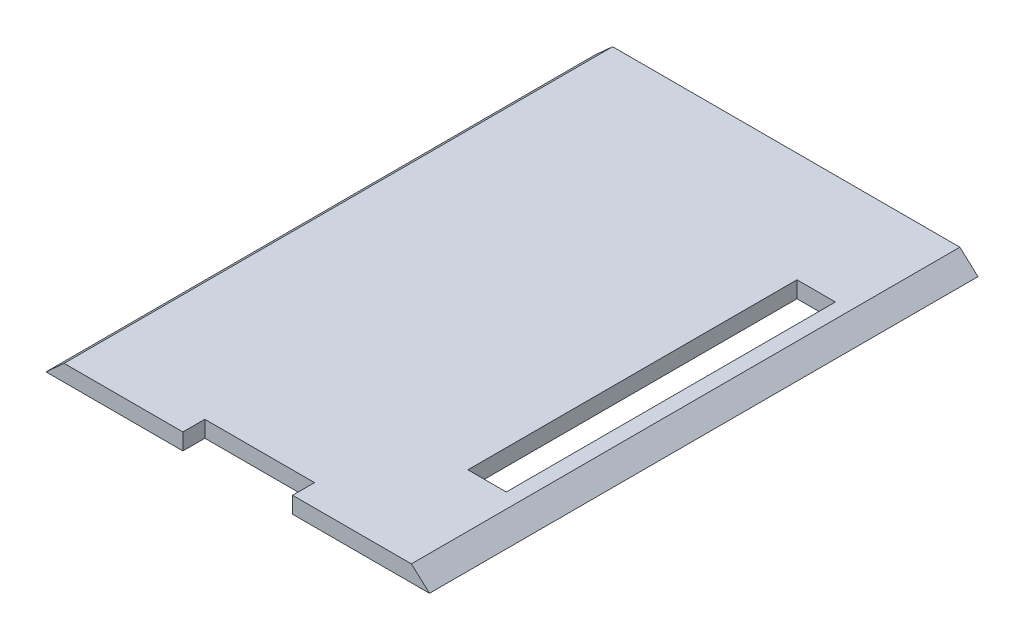
SolidWorks part; units mm, degrees
ref_plane "Front Plane" through (0, 0, 0) normal (0, 0, 1) x (1, 0, 0)
ref_plane "Top Plane" through (0, 0, 0) normal (0, 1, 0) x (1, 0, 0)
ref_plane "Right Plane" through (0, 0, 0) normal (1, 0, 0) x (0, 0, -1)
sketch "Sketch1" plane through (0, 0, 0) normal (0, 0, 1) x (1, 0, 0)
  line L0 (0, 0) -> (0, 44.45) construction
  line L1 (-40.2039, 5.9378) -> (40.2039, 5.9378)
  line L2 (-44.399, 2.1278) -> (44.399, 2.1278)
  line L3 (-40.2039, 5.9378) -> (-44.399, 2.1278)
  line L4 (40.2039, 5.9378) -> (44.399, 2.1278)
  arc A0 (44.399, 2.1278) -> (-44.399, 2.1278) centre (0, 0) ccw construction
  arc A1 (40.2039, 5.9378) -> (-40.2039, 5.9378) centre (0, 0) ccw construction
  dimension "D1" = 88.9
  dimension "D2" = 3.81
  dimension "D3" = 3.81
extrude "Boss-Extrude1" add sketch "Sketch1" along normal blind 127
sketch "Sketch3" plane through (0, 2.1278, 0) normal (0, -1, 0) x (1, 0, 0)
  line L0 (0, 127) -> (0, 0) construction
  line L1 (-44.399, 127) -> (44.399, 127) construction
  line L2 (-44.399, 0) -> (44.399, 0) construction
  line L3 (0, 63.5) -> (44.399, 63.5) construction
  line L4 (-12.7, 127) -> (12.7, 127)
  line L5 (-12.7, 127) -> (-12.7, 121.92)
  line L6 (-12.7, 121.92) -> (12.7, 121.92)
  line L7 (12.7, 127) -> (12.7, 121.92)
  line L8 (44.399, 127) -> (44.399, 0) construction
  line L9 (0, 63.5) -> (-44.399, 63.5) construction
  line L10 (-44.399, 127) -> (-44.399, 0) construction
  line L11 (12.7, -5.08) -> (12.7, 0) construction
  line L13 (-12.7, 0) -> (12.7, 0) construction
  line L14 (-12.7, -5.08) -> (-12.7, 0) construction
  line L15 (-12.7, -5.08) -> (12.7, -5.08) construction
  point P10 (12.7, 124.46)
  dimension "D1" = 25.4
  dimension "D2" = 12.7
  dimension "D3" = 5.08
extrude "Cut-Extrude1" cut sketch "Sketch3" against normal through all
sketch "Sketch5" plane through (0, 2.1278, 0) normal (0, -1, 0) x (1, 0, 0)
  line L0 (12.7, 127) -> (44.399, 127) construction
  line L1 (27.889, 101.6) -> (36.779, 101.6)
  line L2 (27.889, 101.6) -> (27.889, 25.4)
  line L3 (27.889, 25.4) -> (36.779, 25.4)
  line L4 (36.779, 101.6) -> (36.779, 25.4)
  line L5 (44.399, 127) -> (44.399, 0) construction
  dimension "D1" = 76.2
  dimension "D2" = 25.4
  dimension "D3" = 7.62
  dimension "D4" = 8.89
extrude "Cut-Extrude3" cut sketch "Sketch5" against normal through all
